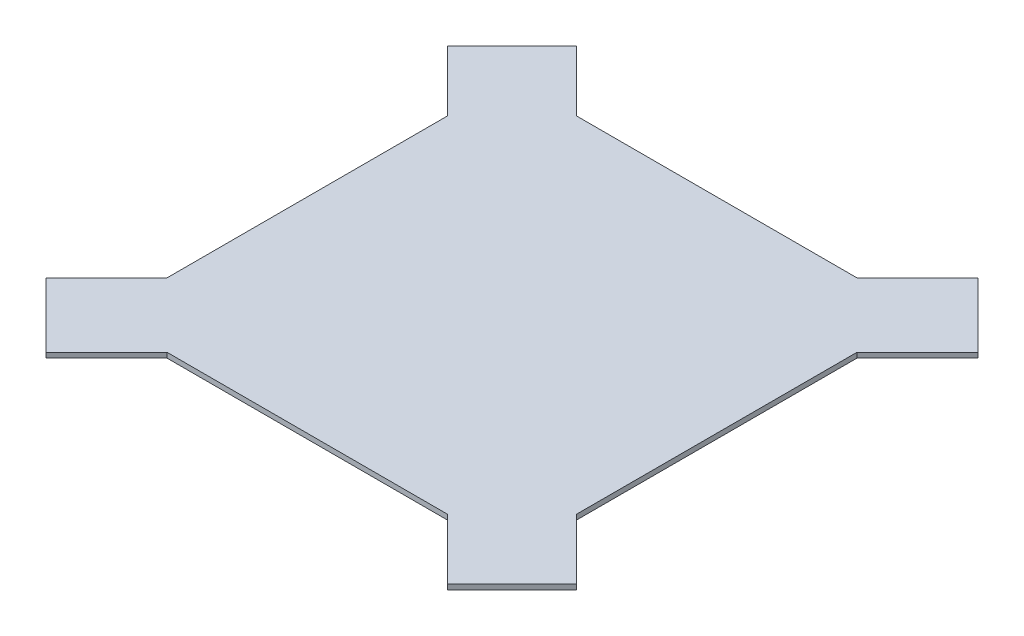
SolidWorks part; units mm, degrees
note: The reader was unsure of these and kept them because the rebuilt part matched: shared geometry of "Sketch39<3>".
ref_plane "Front Plane" through (0, 0, 0) normal (0, 0, 1) x (1, 0, 0)
ref_plane "Top Plane" through (0, 0, 0) normal (0, 1, 0) x (1, 0, 0)
ref_plane "Right Plane" through (0, 0, 0) normal (1, 0, 0) x (0, 0, -1)
sketch "Sketch1" plane through (0, 0, 0) normal (0, 1, 0) x (1, 0, 0)
  line L0 (0, 0) -> (-203.2, 0) construction
  line L1 (254, -381) -> (-254, -381)
  line L2 (381, -254) -> (381, 254)
  line L3 (254, 381) -> (-254, 381)
  line L4 (-381, -254) -> (-381, 254)
  line L5 (381, -381) -> (-381, 381) construction
  line L6 (381, 381) -> (-381, -381) construction
  line L7 (203.2, 152.4) -> (-203.2, 152.4)
  line L8 (203.2, 152.4) -> (203.2, -152.4)
  line L9 (203.2, -152.4) -> (-203.2, -152.4)
  line L10 (-203.2, 152.4) -> (-203.2, -152.4) construction
  line L11 (0, 0) -> (0, 152.4) construction
  line L12 (-254, -381) -> (-381, -254)
  line L13 (-254, 381) -> (-381, 254)
  line L14 (381, 254) -> (254, 381)
  line L15 (381, -254) -> (254, -381)
  point P0 (0, 0)
  point P6 (0, 0)
  dimension "D1" = 762
  dimension "D2" = 762
  dimension "D3" = 304.8
  dimension "D4" = 406.4
  dimension "D5" = 127
  dimension "D6" = 45
  dimension "D7" = 127
  dimension "D8" = 45
  dimension "D9" = 127
  dimension "D10" = 45
  dimension "D11" = 127
  dimension "D12" = 45
extrude "Boss-Extrude1" add sketch "Sketch1" against normal blind 6.35
sketch "Sketch2" [suppressed] plane through (0, 0, 0) normal (0, 1, 0) x (1, 0, 0)
  line L0 (640.2073, 0) -> (-640.2073, 0) construction
  line L1 (0, 0) -> (0, 687.3175) construction
  line L2 (-203.2, 152.4) -> (-203.2, -152.4) construction
  line L3 (203.2, 152.4) -> (-203.2, 152.4) construction
  line L4 (203.2, -152.4) -> (203.2, 152.4) construction
  line L5 (-203.2, -152.4) -> (203.2, -152.4) construction
  line L6 (203.2, 152.4) -> (-203.2, 152.4)
  line L7 (203.2, -152.4) -> (203.2, 152.4)
  line L8 (-203.2, -152.4) -> (203.2, -152.4)
  line L9 (-203.2, 152.4) -> (-203.2, -152.4)
  line L10 (-215.9, 165.1) -> (-215.9, -165.1)
  line L11 (-215.9, -165.1) -> (215.9, -165.1)
  line L12 (215.9, -165.1) -> (215.9, 165.1)
  line L13 (215.9, 165.1) -> (-215.9, 165.1)
  line L14 (203.2, -152.4) -> (228.6, -152.4) construction
  line L15 (228.6, 152.4) -> (203.2, 152.4) construction
  line L16 (228.6, -152.4) -> (215.9, -152.4)
  line L17 (228.6, 152.4) -> (215.9, 152.4)
  line L18 (222.25, -152.4) -> (222.25, 152.4) construction
  line L19 (222.25, 0) -> (374.65, 0) construction
  line L20 (381, -152.4) -> (368.3, -152.4)
  line L21 (381, -254) -> (381, 254) construction
  line L22 (368.3, -152.4) -> (368.3, 152.4)
  line L23 (368.3, 152.4) -> (381, 152.4)
  line L24 (374.65, -152.4) -> (374.65, 152.4) construction
  line L25 (374.65, 0) -> (222.25, 152.4) construction
  line L26 (222.25, 0) -> (374.65, 152.4) construction
  line L27 (374.65, 0) -> (222.25, -152.4) construction
  line L28 (222.25, 0) -> (374.65, -152.4) construction
  line L29 (217.7599, 0) -> (372.4049, 154.6451)
  line L30 (217.7599, 0) -> (372.4049, -154.6451)
  line L31 (370.1599, 0) -> (220.0049, 150.1549)
  line L32 (370.1599, 0) -> (220.0049, -150.1549)
  line L33 (-114.3, -246.761) -> (0, -246.761) construction
  line L34 (-114.3, -350.139) -> (0, -350.139) construction
  line L35 (-114.3, -243.586) -> (0, -243.586)
  line L36 (-114.3, -353.314) -> (0, -353.314)
  line L37 (-114.3, -249.936) -> (0, -249.936)
  line L38 (-114.3, -346.964) -> (0, -346.964)
  line L39 (-114.3, 350.139) -> (-176.911, 350.139) construction
  line L40 (-374.65, 152.4) -> (-176.911, 350.139) construction
  line L41 (-114.3, 246.761) -> (-197.739, 246.761) construction
  line L42 (-197.739, 246.761) -> (-368.3, 76.2) construction
  line L43 (-222.25, 152.4) -> (-352.425, 282.575) construction
  line L44 (-222.25, -152.4) -> (-352.425, -282.575) construction
  line L45 (-368.3, -76.2) -> (-298.45, -76.2) construction
  line L46 (-197.739, -246.761) -> (-368.3, -76.2) construction
  line L47 (-114.3, -246.761) -> (-197.739, -246.761) construction
  line L48 (-374.65, -152.4) -> (-176.911, -350.139) construction
  line L49 (-114.3, -350.139) -> (-176.911, -350.139) construction
  line L50 (-222.25, 0) -> (-374.65, -152.4) construction
  line L51 (228.6, -152.4) -> (228.6, 152.4)
  line L52 (226.7401, 0) -> (376.8951, 150.1549)
  line L53 (226.7401, 0) -> (376.8951, -150.1549)
  line L54 (379.1401, 0) -> (224.4951, 154.6451)
  line L55 (379.1401, 0) -> (224.4951, -154.6451)
  line L56 (114.3, -353.314) -> (114.3, -346.964) construction
  line L57 (114.3, -350.139) -> (176.911, -350.139) construction
  line L58 (374.65, -152.4) -> (176.911, -350.139) construction
  line L59 (114.3, -350.139) -> (0, -350.139) construction
  line L60 (114.3, -249.936) -> (114.3, -243.586) construction
  line L61 (114.3, -246.761) -> (0, -246.761) construction
  line L62 (114.3, -246.761) -> (197.739, -246.761) construction
  line L63 (197.739, -246.761) -> (368.3, -76.2) construction
  line L64 (368.3, -76.2) -> (298.45, -76.2) construction
  line L65 (222.25, -152.4) -> (352.425, -282.575) construction
  line L66 (254, -381) -> (381, -254) construction
  line L67 (217.7599, -152.4) -> (350.1799, -284.8201)
  line L68 (224.4951, -150.1549) -> (354.6701, -280.3299)
  line L69 (220.0049, -154.6451) -> (350.1799, -284.8201) construction
  line L70 (114.3, 246.761) -> (-114.3, 246.761) construction
  line L71 (114.3, 350.139) -> (-114.3, 350.139) construction
  line L72 (114.3, 243.586) -> (-114.3, 243.586)
  line L73 (372.4049, -150.1549) -> (175.5959, -346.964)
  line L74 (114.3, -346.964) -> (175.5959, -346.964)
  line L75 (114.3, -346.964) -> (0, -346.964)
  line L76 (114.3, -249.936) -> (0, -249.936)
  line L77 (114.3, -249.936) -> (199.0541, -249.936)
  line L78 (199.0541, -249.936) -> (368.3, -80.6901)
  line L79 (379.1401, -152.4) -> (178.2261, -353.314)
  line L80 (114.3, -353.314) -> (178.2261, -353.314)
  line L81 (114.3, -353.314) -> (0, -353.314)
  line L82 (114.3, -243.586) -> (0, -243.586)
  line L83 (114.3, -243.586) -> (196.4239, -243.586)
  line L84 (196.4239, -243.586) -> (368.3, -71.7099)
  line L85 (196.4239, -243.586) -> (366.0549, -73.9549) construction
  line L86 (376.8951, -154.6451) -> (178.2261, -353.314) construction
  line L87 (114.3, 353.314) -> (-114.3, 353.314)
  line L88 (199.0541, -249.936) -> (370.5451, -78.4451) construction
  line L89 (114.3, 249.936) -> (-114.3, 249.936)
  line L90 (114.3, 346.964) -> (-114.3, 346.964)
  line L91 (222.25, 152.4) -> (352.425, 282.575) construction
  line L92 (197.739, 246.761) -> (368.3, 76.2) construction
  line L93 (114.3, 246.761) -> (197.739, 246.761) construction
  line L94 (374.65, 152.4) -> (176.911, 350.139) construction
  line L95 (114.3, 350.139) -> (176.911, 350.139) construction
  line L96 (196.4239, 243.586) -> (368.3, 71.7099)
  line L97 (114.3, 243.586) -> (196.4239, 243.586)
  line L98 (114.3, 353.314) -> (178.2261, 353.314)
  line L99 (379.1401, 152.4) -> (178.2261, 353.314)
  line L100 (199.0541, 249.936) -> (368.3, 80.6901)
  line L101 (114.3, 249.936) -> (199.0541, 249.936)
  line L102 (114.3, 346.964) -> (175.5959, 346.964)
  line L103 (372.4049, 150.1549) -> (175.5959, 346.964)
  line L104 (224.4951, 150.1549) -> (354.6701, 280.3299)
  line L105 (217.7599, 152.4) -> (350.1799, 284.8201)
  line L106 (-374.65, 0) -> (-222.25, -152.4) construction
  line L107 (-222.25, 0) -> (-374.65, 152.4) construction
  line L108 (-374.65, 0) -> (-222.25, 152.4) construction
  line L109 (-374.65, -152.4) -> (-374.65, 152.4) construction
  line L110 (-222.25, 0) -> (-374.65, 0) construction
  line L111 (-222.25, -152.4) -> (-222.25, 152.4) construction
  line L112 (-217.7599, 152.4) -> (-350.1799, 284.8201)
  line L113 (-224.4951, 150.1549) -> (-354.6701, 280.3299)
  line L114 (-372.4049, 150.1549) -> (-175.5959, 346.964)
  line L115 (-114.3, 346.964) -> (-175.5959, 346.964)
  line L116 (-114.3, 249.936) -> (-199.0541, 249.936)
  line L117 (-199.0541, 249.936) -> (-368.3, 80.6901)
  line L118 (-379.1401, 152.4) -> (-178.2261, 353.314)
  line L119 (-114.3, 353.314) -> (-178.2261, 353.314)
  line L120 (-114.3, 243.586) -> (-196.4239, 243.586)
  line L121 (-196.4239, 243.586) -> (-368.3, 71.7099)
  line L122 (-196.4239, -243.586) -> (-368.3, -71.7099)
  line L123 (-114.3, -243.586) -> (-196.4239, -243.586)
  line L124 (-114.3, -353.314) -> (-178.2261, -353.314)
  line L125 (-379.1401, -152.4) -> (-178.2261, -353.314)
  line L126 (-199.0541, -249.936) -> (-368.3, -80.6901)
  line L127 (-114.3, -249.936) -> (-199.0541, -249.936)
  line L128 (-114.3, -346.964) -> (-175.5959, -346.964)
  line L129 (-372.4049, -150.1549) -> (-175.5959, -346.964)
  line L130 (-224.4951, -150.1549) -> (-354.6701, -280.3299)
  line L131 (-217.7599, -152.4) -> (-350.1799, -284.8201)
  line L132 (-379.1401, 0) -> (-224.4951, -154.6451)
  line L133 (-379.1401, 0) -> (-224.4951, 154.6451)
  line L134 (-226.7401, 0) -> (-376.8951, -150.1549)
  line L135 (-226.7401, 0) -> (-376.8951, 150.1549)
  line L136 (-228.6, -152.4) -> (-228.6, 152.4)
  line L137 (-370.1599, 0) -> (-220.0049, -150.1549)
  line L138 (-370.1599, 0) -> (-220.0049, 150.1549)
  line L139 (-217.7599, 0) -> (-372.4049, -154.6451)
  line L140 (-217.7599, 0) -> (-372.4049, 154.6451)
  line L141 (-368.3, 152.4) -> (-381, 152.4)
  line L142 (-368.3, -152.4) -> (-368.3, 152.4)
  line L143 (-381, -152.4) -> (-368.3, -152.4)
  line L144 (-228.6, 152.4) -> (-215.9, 152.4)
  line L145 (-228.6, -152.4) -> (-215.9, -152.4)
  line L146 (-368.3, -248.7395) -> (-248.7395, -368.3)
  line L147 (-248.7395, -368.3) -> (248.7395, -368.3)
  line L148 (248.7395, -368.3) -> (368.3, -248.7395)
  line L149 (368.3, -248.7395) -> (368.3, 248.7395)
  line L150 (368.3, 248.7395) -> (248.7395, 368.3)
  line L151 (248.7395, 368.3) -> (-248.7395, 368.3)
  line L152 (-248.7395, 368.3) -> (-368.3, 248.7395)
  line L153 (-368.3, 248.7395) -> (-368.3, -248.7395)
  line L154 (-381, -254) -> (-254, -381)
  line L155 (-254, -381) -> (254, -381)
  line L156 (254, -381) -> (381, -254)
  line L157 (381, -254) -> (381, 254)
  line L158 (381, 254) -> (254, 381)
  line L159 (254, 381) -> (-254, 381)
  line L160 (-254, 381) -> (-381, 254)
  line L161 (-381, 254) -> (-381, -254)
  line L162 (-381, -254) -> (-254, -381)
  line L163 (-254, -381) -> (254, -381)
  line L164 (254, -381) -> (381, -254)
  line L165 (381, -254) -> (381, 254)
  line L166 (381, 254) -> (254, 381)
  line L167 (254, 381) -> (-254, 381)
  line L168 (-254, 381) -> (-381, 254)
  line L169 (-381, 254) -> (-381, -254)
  line L170 (-304.8, 0) -> (-222.25, -82.55)
  line L171 (-304.8, 0) -> (-222.25, 82.55)
  line L172 (-300.3099, 0) -> (-220.0049, -80.3049)
  line L173 (-300.3099, 0) -> (-220.0049, 80.3049)
  line L174 (-309.2901, 0) -> (-224.4951, -84.7951)
  line L175 (-309.2901, 0) -> (-224.4951, 84.7951)
  line L176 (-222.25, 0) -> (-374.65, 0) construction
  line L177 (-222.25, 3.175) -> (-374.65, 3.175)
  line L178 (-222.25, -3.175) -> (-374.65, -3.175)
  line L179 (222.25, 0) -> (374.65, 0) construction
  line L180 (222.25, 0) -> (374.65, 0) construction
  line L181 (222.25, -3.175) -> (374.65, -3.175)
  line L182 (222.25, 3.175) -> (374.65, 3.175)
  line L183 (309.2901, 0) -> (224.4951, 84.7951)
  line L184 (309.2901, 0) -> (224.4951, -84.7951)
  line L185 (300.3099, 0) -> (220.0049, 80.3049)
  line L186 (300.3099, 0) -> (220.0049, -80.3049)
  line L187 (304.8, 0) -> (222.25, 82.55)
  line L188 (304.8, 0) -> (222.25, -82.55)
  circle A0 centre (-114.3, -298.45) radius 48.514
  circle A2 centre (114.3, -298.45) radius 48.514
  circle A3 centre (-114.3, 298.45) radius 48.514
  circle A4 centre (114.3, 298.45) radius 48.514
  circle A5 centre (-114.3, -298.45) radius 54.864
  circle A6 centre (114.3, 298.45) radius 54.864
  circle A7 centre (114.3, -298.45) radius 54.864
  circle A8 centre (-114.3, 298.45) radius 54.864
  point P65 (0, 350.139)
  point P68 (0, 246.761)
  point P70 (0, 346.964)
  point P72 (0, 249.936)
  point P74 (0, 353.314)
  point P76 (0, 243.586)
  dimension "D3" = 97.028
  dimension "D1" = 114.3
  dimension "D2" = 298.45
  dimension "D9" = 3.175
  dimension "D10" = 3.175
  dimension "D11" = 3.175
  dimension "D14" = 3.175
  dimension "D15" = 3.175
  dimension "D16" = 0
  dimension "D7" = 12.7
  dimension "D8" = 12.7
  dimension "D12" = 45
  dimension "D18" = 76.2
  dimension "D4" = 6.35
  dimension "D5" = 6.35
  dimension "D6" = 12.7
  dimension "D13" = 3.175
  dimension "D17" = 12.7
  dimension "D19" = 3.175
  dimension "D20" = 3.175
  dimension "D21" = 3.175
  dimension "D22" = 3.175
sketch "Sketch3" plane through (0, 0, 0) normal (0, 1, 0) x (1, 0, 0)
  line L0 (-251.0461, -331.8684) -> (-175.26, -256.0823)
  line L1 (-254, -381) -> (-381, -254) construction
  line L2 (-175.26, -256.0823) -> (-175.26, -381)
  line L3 (254, -381) -> (-254, -381) construction
  line L4 (-120.65, -224.79) -> (-120.65, -526.5709) construction
  line L5 (-120.65, -279.4) -> (-175.26, -279.4) construction
  line L6 (-317.5, -317.5) -> (0, 0) construction
  line L7 (-331.8684, -251.0461) -> (-256.0823, -175.26)
  line L8 (-256.0823, -175.26) -> (-256.0823, 0)
  line L9 (-3.4925, 0) -> (3.4925, 0) construction
  line L10 (-66.04, -256.0823) -> (-66.04, -381)
  line L11 (-66.04, -256.0823) -> (0, -256.0823)
  line L12 (0, 0) -> (-591.5998, 0) construction
  line L13 (0, 0) -> (0, 686.1368) construction
  line L14 (0, -256.0823) -> (0, -381)
  line L15 (-256.0823, 0) -> (-381, 0)
  line L16 (-381, -254) -> (-381, 254) construction
  line L18 (-66.04, 256.0823) -> (-66.04, 381)
  line L37 (-246.6957, -307.482) -> (-307.482, -246.6957) construction
  line L38 (-251.0461, -331.8684) -> (-331.8684, -251.0461)
  circle A0 centre (-120.65, -279.4) radius 54.61
  circle A1 centre (-120.65, -279.4) radius 48.26
  circle A8 centre (-246.6957, -307.482) radius 3.175 construction
  circle A9 centre (-307.482, -246.6957) radius 3.175 construction
  point P0 (-251.0461, -331.8684)
  point P9 (-333.6238, -249.2907)
  point P23 (-277.0888, -277.0888)
  point P29 (-120.5346, -271.04)
  point P31 (-65.9246, -271.04)
  point P32 (-331.8684, -251.0461)
  point P44 (-256.0823, 0)
  point P71 (0, 256.0823)
  point P72 (0, -256.0823)
  dimension "D2" = 101.6
  dimension "D4" = 6.35
  dimension "D1" = 109.22
  dimension "D7" = 6.35
  dimension "D3" = 85.9648
  dimension "D5" = 114.3
  dimension "D6" = 57.15
  dimension "D8" = 20.32
  dimension "D10" = 120.65
extrude "Cut-Extrude1" cut sketch "Sketch3" against normal up to next
hole_wizard "#4 Clearance Hole2" [suppressed] positions "Sketch17" profile "Sketch19" hole size "#4" standard "ANSI Inch"
sketch "Sketch17" plane through (0, 0, 0) normal (0, 1, 0) x (1, 0, 0)
  point P0 (-307.482, -246.6957)
  point P3 (-246.6957, -307.482)
sketch "Sketch19" plane through (-307.482, 0, 246.6957) normal (1, 0, 0) x (0, 0, 1)
  line L0 (0, 0) -> (0, 6.35)
  line L1 (0, 6.35) -> (1.4732, 6.35)
  line L2 (1.4732, 6.35) -> (1.4732, 0)
  line L5 (1.4732, 0) -> (0, 0)
  line L11 (0, -6.35) -> (0, 107.95) construction
  dimension "Thru Hole Dia." = 2.9464
  dimension "Thru Hole Depth" = 6.35
mirror "Mirror1" about plane through (0, 0, 0) normal (1, 0, 0) of "#4 Clearance Hole2", "Cut-Extrude1"
mirror "Mirror2" about plane through (0, 0, 0) normal (0, 0, 1) of "Mirror1", "Cut-Extrude1"
sketch "Sketch12" [suppressed] plane through (0, 0, 0) normal (0, 1, 0) x (1, 0, 0)
  line L0 (120.65, -279.4) -> (120.65, -223.52) construction
  line L1 (120.65, -223.52) -> (132.08, -223.52) construction
  line L2 (120.65, -279.4) -> (132.08, -223.52) construction
  circle A0 centre (120.65, -279.4) radius 48.26 construction
  circle A1 centre (120.65, -279.4) radius 48.26 construction
  circle A2 centre (132.08, -223.52) radius 2.9268
  circle A3 centre (126.365, -233.4187) radius 2.9268 [skipped]
  circle A4 centre (114.935, -233.4187) radius 2.9268 [skipped]
  circle A5 centre (109.22, -223.52) radius 2.9268
  circle A8 centre (114.935, -213.6214) radius 2.9268 [skipped]
  circle A9 centre (126.365, -213.6214) radius 2.9268 [skipped]
  point P8 (120.65, -223.52)
  point P19 (120.65, -223.52)
  dimension "D3" = 5.8535
  dimension "D1" = 57.037
  dimension "D2" = 22.86
  dimension "D4" = 6
hole_wizard "#4 Clearance Hole1" [suppressed] positions "Sketch14" profile "Sketch16" hole size "#4" standard "ANSI Inch"
sketch "Sketch14" [suppressed] plane through (0, 0, 0) normal (0, 1, 0) x (1, 0, 0)
  point P0 (109.22, -223.52)
  point P3 (132.08, -223.52)
sketch "Sketch16" [suppressed] plane through (109.22, 0, 223.52) normal (1, 0, 0) x (0, 0, 1)
  line L0 (0, 0) -> (0, 6.35)
  line L1 (0, 6.35) -> (1.6319, 6.35)
  line L2 (1.6319, 6.35) -> (1.6319, 0)
  line L5 (1.6319, 0) -> (0, 0)
  line L11 (0, -6.35) -> (0, 107.95) construction
  dimension "Thru Hole Dia." = 3.2639
  dimension "Thru Hole Depth" = 6.35
sketch "Sketch13" [suppressed] plane through (0, -6.35, 0) normal (0, -1, 0) x (1, 0, 0)
  line L0 (-307.482, -246.6957) -> (-287.3581, -266.8195) construction
  line L1 (-287.3581, -266.8195) -> (-266.8195, -287.3581) construction
  line L2 (-266.8195, -287.3581) -> (-246.6957, -307.482) construction
  line L3 (-278.3779, -257.8393) -> (-257.8393, -278.3779)
  line L4 (-296.3384, -275.7998) -> (-275.7998, -296.3384)
  arc A0 (-278.3779, -257.8393) -> (-296.3384, -275.7998) centre (-287.3581, -266.8195) ccw
  arc A2 (-275.7998, -296.3384) -> (-257.8393, -278.3779) centre (-266.8195, -287.3581) ccw
  dimension "D1" = 29.046
  dimension "D2" = 25.4
extrude "Cut-Extrude10" [suppressed] cut sketch "Sketch13" against normal through all
mirror "Mirror3" [suppressed] about plane through (0, 0, 0) normal (1, 0, 0)
mirror "Mirror4" [suppressed] about plane through (0, 0, 0) normal (0, 0, 1)
sketch "Sketch4" [suppressed] plane through (0, 0, 0) normal (0, 1, 0) x (1, 0, 0)
  line L22 (-182.88, 152.4) -> (-182.88, 170.18) construction
  line L23 (-203.2, -152.4) -> (203.2, -152.4) construction
  line L24 (-203.2, -152.4) -> (-203.2, 152.4) construction
  line L25 (-203.2, 152.4) -> (203.2, 152.4) construction
  line L26 (203.2, -152.4) -> (203.2, 152.4) construction
  line L27 (-203.2, -152.4) -> (203.2, 152.4) construction
  line L28 (-203.2, 152.4) -> (203.2, -152.4) construction
  line L29 (-182.88, 170.18) -> (-220.98, 170.18) construction
  line L30 (-220.98, 170.18) -> (-220.98, 132.08) construction
  line L31 (-220.98, 132.08) -> (-203.2, 132.08) construction
  line L32 (-203.2, 152.4) -> (-220.98, 170.18) construction
  line L33 (-214.63, 132.08) -> (-214.63, 138.43) construction
  line L39 (-214.63, 138.43) -> (-214.63, 151.13) construction
  line L40 (-214.63, 151.13) -> (-214.63, 163.83) construction
  line L41 (203.2, 0) -> (-203.2, 0) construction
  line L42 (0, 152.4) -> (0, -152.4) construction
  line L43 (0, 163.83) -> (12.7, 163.83) construction
  line L44 (12.7, 163.83) -> (25.4, 163.83) construction
  line L45 (25.4, 163.83) -> (31.75, 163.83) construction
  line L46 (25.4, -163.83) -> (31.75, -163.83) construction
  line L47 (12.7, -163.83) -> (25.4, -163.83) construction
  line L48 (0, -163.83) -> (12.7, -163.83) construction
  circle A29 centre (-214.63, 138.43) radius 2.5527
  circle A30 centre (-214.63, 151.13) radius 2.5527
  circle A31 centre (-214.63, 163.83) radius 2.5527
  circle A32 centre (-201.93, 163.83) radius 2.5527
  circle A33 centre (-189.23, 163.83) radius 2.5527
  circle A34 centre (0, 163.83) radius 2.5527
  circle A35 centre (25.4, 163.83) radius 2.5527
  circle A36 centre (12.7, 163.83) radius 2.5527
  circle A37 centre (-12.7, 163.83) radius 2.5527
  circle A38 centre (-25.4, 163.83) radius 2.5527
  circle A39 centre (201.93, 163.83) radius 2.5527
  circle A40 centre (189.23, 163.83) radius 2.5527
  circle A41 centre (214.63, 163.83) radius 2.5527
  circle A42 centre (214.63, 151.13) radius 2.5527
  circle A43 centre (214.63, 138.43) radius 2.5527
  circle A44 centre (-214.63, -138.43) radius 2.5527
  circle A45 centre (-214.63, -151.13) radius 2.5527
  circle A46 centre (-214.63, -163.83) radius 2.5527
  circle A47 centre (-189.23, -163.83) radius 2.5527
  circle A48 centre (-201.93, -163.83) radius 2.5527
  circle A49 centre (-25.4, -163.83) radius 2.5527
  circle A50 centre (-12.7, -163.83) radius 2.5527
  circle A51 centre (12.7, -163.83) radius 2.5527
  circle A52 centre (25.4, -163.83) radius 2.5527
  circle A53 centre (0, -163.83) radius 2.5527
  circle A54 centre (189.23, -163.83) radius 2.5527
  circle A55 centre (201.93, -163.83) radius 2.5527
  circle A56 centre (214.63, -138.43) radius 2.5527
  circle A57 centre (214.63, -151.13) radius 2.5527
  circle A58 centre (214.63, -163.83) radius 2.5527
  point P0 (0, 0)
  point P12 (-214.63, 138.43)
  point P14 (-214.63, 151.13)
  dimension "D6" = 6.35
  dimension "D7" = 5.1054
  dimension "D8" = 5.1054
  dimension "D1" = 304.8
  dimension "D2" = 406.4
  dimension "D3" = 38.1
  dimension "D4" = 17.78
  dimension "D5" = 6.35
  dimension "D9" = 11.43
  dimension "D10" = 31.75
  dimension "D11" = 6.35
hole_wizard "#4-40 Tapped Hole1" [suppressed] positions "Sketch20" profile "Sketch21" tap size "#4-40" standard "ANSI Inch"
sketch "Sketch20" [suppressed] plane through (0, -6.35, 0) normal (0, -1, 0) x (-1, 0, 0)
  line L0 (214.63, 138.43) -> (214.63, 151.13) construction
  point P0 (189.23, -163.83)
  point P3 (201.93, -163.83)
  point P6 (214.63, -163.83)
  point P9 (214.63, -151.13)
  point P12 (214.63, -138.43)
  point P15 (25.4, -163.83)
  point P18 (12.7, -163.83)
  point P21 (0, -163.83)
  point P24 (-12.7, -163.83)
  point P27 (-25.4, -163.83)
  point P30 (-189.23, -163.83)
  point P33 (-201.93, -163.83)
  point P36 (-214.63, -163.83)
  point P39 (-214.63, -151.13)
  point P42 (-214.63, -138.43)
  point P46 (214.63, 138.43)
  point P49 (214.63, 151.13)
  point P58 (214.63, 163.83)
  point P61 (201.93, 163.83)
  point P64 (189.23, 163.83)
  point P67 (25.4, 163.83)
  point P70 (12.7, 163.83)
  point P73 (0, 163.83)
  point P76 (-12.7, 163.83)
  point P79 (-25.4, 163.83)
  point P82 (-214.63, 163.83)
  point P85 (-214.63, 151.13)
  point P88 (-214.63, 138.43)
  point P91 (-201.93, 163.83)
  point P94 (-189.23, 163.83)
sketch "Sketch21" [suppressed] plane through (-189.23, -6.35, 163.83) normal (1, 0, 0) x (0, 0, -1)
  line L0 (0, 0) -> (0, 6.35)
  line L1 (0, 6.35) -> (1.1303, 6.35)
  line L2 (1.1303, 6.35) -> (1.1303, 0)
  line L5 (1.1303, 0) -> (0, 0)
  line L11 (0, -6.35) -> (0, 107.95) construction
  dimension "Thru Tap Drill Dia." = 2.2606
  dimension "Thru Tap Drill Depth" = 6.35
cosmetic thread "Hole Thread3" [suppressed] parameters "D2"=2.8448
cosmetic thread "Hole Thread4" [suppressed] parameters "D2"=2.8448
cosmetic thread "Hole Thread5" [suppressed] parameters "D2"=2.8448
cosmetic thread "Hole Thread6" [suppressed] parameters "D2"=2.8448
cosmetic thread "Hole Thread7" [suppressed] parameters "D2"=2.8448
cosmetic thread "Hole Thread8" [suppressed] parameters "D2"=2.8448
cosmetic thread "Hole Thread9" [suppressed] parameters "D2"=2.8448
cosmetic thread "Hole Thread10" [suppressed] parameters "D2"=2.8448
cosmetic thread "Hole Thread11" [suppressed] parameters "D2"=2.8448
cosmetic thread "Hole Thread12" [suppressed] parameters "D2"=2.8448
cosmetic thread "Hole Thread13" [suppressed] parameters "D2"=2.8448
cosmetic thread "Hole Thread14" [suppressed] parameters "D2"=2.8448
cosmetic thread "Hole Thread15" [suppressed] parameters "D2"=2.8448
cosmetic thread "Hole Thread16" [suppressed] parameters "D2"=2.8448
cosmetic thread "Hole Thread17" [suppressed] parameters "D2"=2.8448
cosmetic thread "Hole Thread18" [suppressed] parameters "D2"=2.8448
cosmetic thread "Hole Thread19" [suppressed] parameters "D2"=2.8448
cosmetic thread "Hole Thread20" [suppressed] parameters "D2"=2.8448
cosmetic thread "Hole Thread21" [suppressed] parameters "D2"=2.8448
cosmetic thread "Hole Thread22" [suppressed] parameters "D2"=2.8448
cosmetic thread "Hole Thread23" [suppressed] parameters "D2"=2.8448
cosmetic thread "Hole Thread24" [suppressed] parameters "D2"=2.8448
cosmetic thread "Hole Thread25" [suppressed] parameters "D2"=2.8448
cosmetic thread "Hole Thread26" [suppressed] parameters "D2"=2.8448
cosmetic thread "Hole Thread27" [suppressed] parameters "D2"=2.8448
cosmetic thread "Hole Thread28" [suppressed] parameters "D2"=2.8448
cosmetic thread "Hole Thread29" [suppressed] parameters "D2"=2.8448
cosmetic thread "Hole Thread30" [suppressed] parameters "D2"=2.8448
cosmetic thread "Hole Thread31" [suppressed] parameters "D2"=2.8448
cosmetic thread "Hole Thread32" [suppressed] parameters "D2"=2.8448
sketch "Sketch5" [suppressed] plane through (0, 0, 0) normal (0, 1, 0) x (1, 0, 0)
  line L6 (-88.9, -44.45) -> (88.9, -44.45)
  line L12 (-88.9, -44.45) -> (-88.9, 44.45)
  line L13 (-88.9, 44.45) -> (88.9, 44.45)
  line L14 (88.9, -44.45) -> (88.9, 44.45)
  line L15 (-88.9, -44.45) -> (88.9, 44.45) construction
  line L16 (-88.9, 44.45) -> (88.9, -44.45) construction
  point P0 (0, 0)
  dimension "D1" = 88.9
  dimension "D2" = 177.8
extrude "Cut-Extrude3" [suppressed] cut sketch "Sketch5" against normal up to next
fillet "Fillet1" [suppressed] radius 8.89
sketch "Sketch8" [suppressed] plane through (0, 0, 0) normal (0, 1, 0) x (1, 0, 0)
  line L0 (66.04, 256.0823) -> (-66.04, 256.0823) construction
  line L1 (66.04, 256.0823) -> (66.04, 279.4) construction
  line L2 (0, 0) -> (0, -256.0823) construction
  line L3 (0, 0) -> (256.0823, 0) construction
  line L4 (256.0823, -175.26) -> (256.0823, 175.26) construction
  line L5 (-66.04, -256.0823) -> (66.04, -256.0823) construction
  circle A0 centre (78.74, 201.4723) radius 10
  circle A1 centre (-78.74, 201.4723) radius 10
  circle A2 centre (-78.74, -201.4723) radius 10
  circle A3 centre (78.74, -201.4723) radius 10
  dimension "D1" = 20
  dimension "D2" = 54.61
  dimension "D3" = 12.7
extrude "Cut-Extrude6" [suppressed] cut sketch "Sketch8" against normal up to next
hole_wizard "#10-32 Tapped Hole2" [suppressed] positions "Sketch24" profile "Sketch25" tap size "#10-32" standard "ANSI Inch"
sketch "Sketch24" plane through (0, -6.35, 0) normal (0, -1, 0) x (-1, 0, 0)
  line L3 (0, 0) -> (256.0823, 0) construction
  line L4 (256.0823, 175.26) -> (256.0823, -175.26) construction
  line L6 (228.6, 0) -> (228.6, 25.4) construction
  line L7 (228.6, 25.4) -> (256.0823, 25.4) construction
  point P143 (228.6, 25.4)
  dimension "D1" = 228.6
  dimension "D2" = 25.4
cosmetic thread "Hole Thread33" [suppressed] parameters "D2"=4.826
sketch "Sketch25" plane through (-228.6, -6.35, -25.4) normal (1, 0, 0) x (0, 0, -1)
  line L0 (0, 0) -> (0, 6.35)
  line L1 (0, 6.35) -> (2.0193, 6.35)
  line L2 (2.0193, 6.35) -> (2.0193, 0)
  line L5 (2.0193, 0) -> (0, 0)
  line L11 (0, -6.35) -> (0, 107.95) construction
  dimension "Thru Tap Drill Dia." = 4.0386
  dimension "Thru Tap Drill Depth" = 6.35
pattern_linear "LPattern1" [suppressed] count 6 spacing 25.4 count 3 spacing 50.8
hole_wizard "#10-32 Tapped Hole3" [suppressed] positions "Sketch26" profile "Sketch27" tap size "#10-32" standard "ANSI Inch"
sketch "Sketch26" plane through (0, -6.35, 0) normal (0, -1, 0) x (-1, 0, 0)
  line L0 (0, 0) -> (76.2, 0) construction
  line L1 (76.2, 0) -> (76.2, 76.2) construction
  point P0 (76.2, 76.2)
  dimension "D1" = 76.2
  dimension "D2" = 76.2
sketch "Sketch27" plane through (-76.2, -6.35, -76.2) normal (1, 0, 0) x (0, 0, -1)
  line L0 (0, 0) -> (0, 6.35)
  line L1 (0, 6.35) -> (2.0193, 6.35)
  line L2 (2.0193, 6.35) -> (2.0193, 0)
  line L5 (2.0193, 0) -> (0, 0)
  line L11 (0, -6.35) -> (0, 107.95) construction
  dimension "Thru Tap Drill Dia." = 4.0386
  dimension "Thru Tap Drill Depth" = 6.35
cosmetic thread "Hole Thread34" [suppressed] parameters "D2"=4.826
pattern_linear "LPattern2" [suppressed] count 4 spacing 25.4 count 2 spacing 50.8
mirror "Mirror7" [suppressed] about plane through (0, 0, 0) normal (1, 0, 0)
mirror "Mirror8" [suppressed] about plane through (0, 0, 0) normal (0, 0, 1)
fillet "Fillet5" [suppressed] radius 3.175
fillet "Fillet6" [suppressed] radius 12.7
sketch "Sketch22" [suppressed] plane through (0, -6.35, 0) normal (0, -1, 0) x (1, 0, 0)
  line L0 (0, 256.0823) -> (0, 210.3623) construction
  line L1 (-57.15, 182.4223) -> (57.15, 182.4223)
  line L3 (-57.15, 238.3023) -> (57.15, 238.3023)
  line L5 (-57.15, 182.4223) -> (57.15, 238.3023) construction
  line L6 (-57.15, 238.3023) -> (57.15, 182.4223) construction
  line L7 (53.34, 256.0823) -> (-53.34, 256.0823) construction
  line L8 (0, 210.3623) -> (0, 44.45) construction
  line L9 (80.01, 44.45) -> (-80.01, 44.45) construction
  line L10 (57.15, 238.3023) -> (95.25, 210.3623)
  line L11 (95.25, 210.3623) -> (57.15, 182.4223)
  line L12 (-57.15, 238.3023) -> (-95.25, 210.3623)
  line L13 (-95.25, 210.3623) -> (-57.15, 182.4223)
  line L14 (268.1086, 268.1086) -> (196.2665, 196.2665) construction
  line L15 (257.8393, 278.3779) -> (278.3779, 257.8393) construction
  line L16 (196.2665, 253.7402) -> (232.1876, 289.6612)
  line L17 (196.2665, 253.7402) -> (253.7402, 196.2665) construction
  line L18 (232.1876, 289.6612) -> (289.6612, 232.1876)
  line L19 (253.7402, 196.2665) -> (289.6612, 232.1876)
  line L20 (196.2665, 253.7402) -> (289.6612, 232.1876) construction
  line L21 (232.1876, 289.6612) -> (253.7402, 196.2665) construction
  line L22 (196.2665, 253.7402) -> (196.2665, 196.2665) construction
  line L23 (196.2665, 196.2665) -> (253.7402, 196.2665)
  line L24 (196.2665, 253.7402) -> (138.7929, 196.2665)
  line L25 (138.7929, 196.2665) -> (196.2665, 196.2665)
  point P0 (0, 210.3623)
  point P15 (242.9639, 242.9639)
  dimension "D1" = 114.3
  dimension "D2" = 55.88
  dimension "D3" = 17.78
  dimension "D4" = 38.1
  dimension "D5" = 81.28
  dimension "D6" = 50.8
  dimension "D7" = 10.16
extrude "Cut-Extrude11" [suppressed] cut sketch "Sketch22" against normal through all
sketch "Sketch23" [suppressed] plane through (0, -6.35, 0) normal (0, -1, 0) x (1, 0, 0)
  line L0 (57.15, 238.3023) -> (57.15, 182.4223) construction
  line L1 (57.15, 182.4223) -> (-57.15, 238.3023) construction
  line L2 (-57.15, 238.3023) -> (-57.15, 182.4223) construction
  line L3 (-57.15, 182.4223) -> (57.15, 238.3023) construction
  line L4 (-54.61, 186.4914) -> (-5.7831, 210.3623)
  line L5 (54.61, 186.4914) -> (5.7831, 210.3623)
  line L6 (-59.69, 242.3714) -> (-59.69, 178.3532)
  line L7 (59.69, 242.3714) -> (59.69, 178.3532)
  line L8 (59.69, 178.3532) -> (0, 207.535)
  line L9 (-54.61, 234.2332) -> (-54.61, 186.4914)
  line L10 (-59.69, 178.3532) -> (0, 207.535)
  line L11 (232.1876, 289.6612) -> (253.7402, 196.2665) construction
  line L12 (59.69, 238.3023) -> (59.69, 178.3532) construction
  line L13 (253.7402, 196.2665) -> (196.2665, 253.7402) construction
  line L14 (-59.69, 242.3714) -> (-59.69, 182.4223) construction
  line L15 (-56.0344, 180.1404) -> (58.2656, 236.0204) construction
  line L16 (-5.7831, 210.3623) -> (-54.61, 234.2332)
  line L17 (59.69, 178.3532) -> (-54.61, 234.2332) construction
  line L18 (0, 213.1896) -> (59.69, 242.3714)
  line L19 (5.7831, 210.3623) -> (54.61, 234.2332)
  line L20 (0, 213.1896) -> (-59.69, 242.3714)
  line L21 (54.61, 186.4914) -> (-59.69, 242.3714) construction
  line L22 (54.61, 234.2332) -> (54.61, 186.4914)
  line L23 (54.61, 238.3023) -> (54.61, 186.4914) construction
  line L24 (196.2665, 253.7402) -> (289.6612, 232.1876) construction
  line L25 (-54.61, 234.2332) -> (-54.61, 182.4223) construction
  line L26 (196.2665, 196.2665) -> (225.0034, 225.0034) construction
  line L27 (196.2665, 192.6744) -> (225.0034, 221.4113)
  line L28 (229.7126, 289.0901) -> (239.5751, 246.3527)
  line L29 (249.2738, 204.3251) -> (204.3251, 249.2738)
  line L31 (234.6625, 290.2323) -> (245.0819, 245.0819)
  line L32 (258.2066, 188.208) -> (225.0034, 221.4113)
  line L33 (204.3251, 249.2738) -> (240.8459, 240.8459)
  line L34 (188.208, 258.2066) -> (239.5751, 246.3527)
  line L36 (258.2066, 188.208) -> (194.4705, 251.9441) construction
  line L37 (196.8377, 256.2151) -> (290.2323, 234.6625) construction
  line L38 (290.2323, 234.6625) -> (289.0901, 229.7126)
  line L39 (229.7126, 289.0901) -> (234.6625, 290.2323)
  line L40 (198.8065, 190.1344) -> (165.7337, 223.2073) construction
  line L41 (198.0626, 194.4705) -> (226.7994, 223.2073) construction
  line L42 (221.4113, 225.0034) -> (198.8065, 247.6081)
  line L43 (245.0819, 245.0819) -> (290.2323, 234.6625)
  line L44 (246.3527, 239.5751) -> (258.2066, 188.208)
  line L45 (234.6625, 290.2323) -> (258.2066, 188.208) construction
  line L46 (246.3527, 239.5751) -> (289.0901, 229.7126)
  line L47 (195.6954, 251.2652) -> (289.0901, 229.7126) construction
  line L48 (240.8459, 240.8459) -> (249.2738, 204.3251)
  line L49 (229.7126, 289.0901) -> (249.2738, 204.3251) construction
  line L50 (196.2665, 196.2665) -> (225.0034, 225.0034) construction
  line L51 (249.2738, 204.3251) -> (198.0626, 255.5362) construction
  line L52 (196.2665, 253.7402) -> (196.2665, 196.2665) construction
  line L53 (196.2665, 253.7402) -> (196.2665, 196.2665) construction
  line L54 (196.2665, 196.2665) -> (167.5297, 225.0034) construction
  line L55 (196.2665, 253.7402) -> (138.7929, 196.2665) construction
  line L56 (193.7265, 252.6881) -> (193.7265, 202.3986)
  line L57 (193.7265, 202.3986) -> (169.3258, 226.7994)
  line L58 (193.7265, 253.7402) -> (193.7265, 202.3986) construction
  line L59 (196.2665, 192.6744) -> (165.7337, 223.2073)
  line L60 (165.7337, 223.2073) -> (169.3258, 226.7994)
  line L61 (198.8065, 202.3986) -> (221.4113, 225.0034)
  line L63 (198.8065, 253.7402) -> (198.8065, 190.1344) construction
  line L64 (198.8065, 247.6081) -> (198.8065, 202.3986)
  line L65 (193.7265, 252.6881) -> (188.208, 258.2066)
  dimension "D4" = 2.54
  dimension "D5" = 2.54
  dimension "D6" = 2.54
  dimension "D13" = 2.54
  dimension "D14" = 5.08
  dimension "D1" = 2.54
  dimension "D2" = 2.54
  dimension "D3" = 2.54
  dimension "D7" = 2.54
  dimension "D8" = 2.54
  dimension "D9" = 2.54
  dimension "D10" = 2.54
  dimension "D11" = 2.54
  dimension "D12" = 2.54
extrude "Boss-Extrude2" [suppressed] add sketch "Sketch23" against normal up to surface (6.35 mm away)
fillet "Fillet7" [suppressed] radius 3.81
mirror "Mirror5" [suppressed] about plane through (0, 0, 0) normal (1, 0, 0)
mirror "Mirror6" [suppressed] about plane through (0, 0, 0) normal (0, 0, 1)
sketch "Sketch28" [suppressed] plane through (0, -6.35, 0) normal (0, -1, 0) x (1, 0, 0)
  line L1 (-190.5, 127) -> (190.5, 127) construction
  line L2 (-190.5, 127) -> (-190.5, -127) construction
  line L3 (-190.5, -127) -> (190.5, -127) construction
  line L4 (190.5, 127) -> (190.5, -127) construction
  line L5 (-190.5, 127) -> (190.5, -127) construction
  line L6 (-190.5, -127) -> (190.5, 127) construction
  circle A0 centre (190.5, 127) radius 2.5527
  circle A1 centre (139.7, 127) radius 2.5527
  circle A2 centre (88.9, 127) radius 2.5527
  circle A3 centre (38.1, 127) radius 2.5527
  circle A4 centre (-12.7, 127) radius 2.5527
  circle A5 centre (-63.5, 127) radius 2.5527
  circle A6 centre (-114.3, 127) radius 2.5527
  circle A7 centre (-165.1, 127) radius 2.5527
  circle A8 centre (-215.9, 127) radius 2.5527
  circle A9 centre (139.7, 76.2) radius 2.5527
  circle A10 centre (88.9, 76.2) radius 2.5527
  circle A11 centre (38.1, 76.2) radius 2.5527
  circle A12 centre (-12.7, 76.2) radius 2.5527
  circle A13 centre (-63.5, 76.2) radius 2.5527
  circle A14 centre (-114.3, 76.2) radius 2.5527
  circle A15 centre (-165.1, 76.2) radius 2.5527
  circle A16 centre (-215.9, 76.2) radius 2.5527
  circle A17 centre (139.7, 25.4) radius 2.5527
  circle A18 centre (88.9, 25.4) radius 2.5527
  circle A19 centre (38.1, 25.4) radius 2.5527
  circle A20 centre (-12.7, 25.4) radius 2.5527
  circle A21 centre (-63.5, 25.4) radius 2.5527
  circle A22 centre (-114.3, 25.4) radius 2.5527
  circle A23 centre (-165.1, 25.4) radius 2.5527
  circle A24 centre (-215.9, 25.4) radius 2.5527
  circle A25 centre (139.7, -25.4) radius 2.5527
  circle A26 centre (88.9, -25.4) radius 2.5527
  circle A27 centre (38.1, -25.4) radius 2.5527
  circle A28 centre (-12.7, -25.4) radius 2.5527
  circle A29 centre (-63.5, -25.4) radius 2.5527
  circle A30 centre (-114.3, -25.4) radius 2.5527
  circle A31 centre (-165.1, -25.4) radius 2.5527
  circle A32 centre (-215.9, -25.4) radius 2.5527
  circle A33 centre (139.7, -76.2) radius 2.5527
  circle A34 centre (88.9, -76.2) radius 2.5527
  circle A35 centre (38.1, -76.2) radius 2.5527
  circle A36 centre (-12.7, -76.2) radius 2.5527
  circle A37 centre (-63.5, -76.2) radius 2.5527
  circle A38 centre (-114.3, -76.2) radius 2.5527
  circle A39 centre (-165.1, -76.2) radius 2.5527
  circle A40 centre (-215.9, -76.2) radius 2.5527
  circle A41 centre (139.7, -127) radius 2.5527
  circle A42 centre (88.9, -127) radius 2.5527
  circle A43 centre (38.1, -127) radius 2.5527
  circle A44 centre (-12.7, -127) radius 2.5527
  circle A45 centre (-63.5, -127) radius 2.5527
  circle A46 centre (-114.3, -127) radius 2.5527
  circle A47 centre (-165.1, -127) radius 2.5527
  circle A48 centre (-215.9, -127) radius 2.5527
  circle A49 centre (139.7, -177.8) radius 2.5527
  circle A50 centre (88.9, -177.8) radius 2.5527
  circle A51 centre (38.1, -177.8) radius 2.5527
  circle A52 centre (-12.7, -177.8) radius 2.5527
  circle A53 centre (-63.5, -177.8) radius 2.5527
  circle A54 centre (-114.3, -177.8) radius 2.5527
  circle A55 centre (-165.1, -177.8) radius 2.5527
  circle A56 centre (-215.9, -177.8) radius 2.5527
  circle A57 centre (190.5, 76.2) radius 2.5527
  circle A58 centre (190.5, 25.4) radius 2.5527
  circle A59 centre (190.5, -25.4) radius 2.5527
  circle A60 centre (190.5, -76.2) radius 2.5527
  circle A61 centre (190.5, -127) radius 2.5527
  circle A62 centre (190.5, -177.8) radius 2.5527
  point P0 (0, 0)
  dimension "D1" = 254
  dimension "D3" = 5.1054
  dimension "D2" = 381
  dimension "D4" = 7
hole_wizard "1/4-20 Tapped Hole2" [suppressed] positions "Sketch37" profile "Sketch38" tap size "1/4-20" standard "ANSI Inch"
sketch "Sketch37" [suppressed] plane through (0, -6.35, 0) normal (0, -1, 0) x (-1, 0, 0)
  point P0 (-190.5, 127)
sketch "Sketch38" [suppressed] plane through (190.5, -6.35, -127) normal (1, 0, 0) x (0, 0, -1)
  line L0 (0, 0) -> (0, 6.35)
  line L1 (0, 6.35) -> (2.5527, 6.35)
  line L2 (2.5527, 6.35) -> (2.5527, 0)
  line L5 (2.5527, 0) -> (0, 0)
  line L11 (0, -6.35) -> (0, 107.95) construction
  dimension "Thread Major Dia." = 5.1054
  dimension "Thru Tap Drill Depth" = 6.35
pattern_linear "LPattern10" [suppressed] count 6 spacing 50.8 count 11 spacing 38.1
sketch "Sketch39" plane through (0, -6.35, 0) normal (0, -1, 0) x (1, 0, 0)
  line L0 (175.26, -256.0823) -> (-175.26, -256.0823)
  line L1 (-175.26, -256.0823) -> (-175.26, -177.0982)
  line L2 (-175.26, -177.0982) -> (175.26, -177.0982)
  line L3 (175.26, -177.0982) -> (175.26, -256.0823)
  line L4 (175.26, -256.0823) -> (175.26, -357.6769)
  line L5 (175.26, -357.6769) -> (-175.26, -357.6769)
  line L6 (-175.26, -357.6769) -> (-175.26, -256.0823)
  circle M3 centre (120.65, -279.4) radius 48.26
  line M10 (-175.26, -256.0823) -> (-175.26, -279.4)
  arc M11 (-175.26, -279.4) -> (-66.04, -279.4) centre (-120.65, -279.4) ccw
  line M12 (-66.04, -279.4) -> (-66.04, -256.0823)
  line M14 (66.04, -256.0823) -> (66.04, -279.4)
  arc M15 (66.04, -279.4) -> (175.26, -279.4) centre (120.65, -279.4) ccw
  line M16 (175.26, -279.4) -> (175.26, -256.0823)
  circle M40 centre (-120.65, -279.4) radius 48.26
extrude "Boss-Extrude3" add sketch "Sketch39" against normal blind 6.35 contours L0 M3 | L0 M40
extrude "Cut-Extrude12" cut sketch "Sketch39<3>" against normal blind 55.372 contours L0 M16 M3 M14 M15 | L0 M12 M40 M10 M11
sketch "Sketch39<3>" plane through (0, -6.35, 0) normal (0, -1, 0) x (1, 0, 0) same geometry as "Sketch39"
mirror "Mirror9" about plane through (0, 0, 0) normal (0, 0, 1) of "Cut-Extrude12", "Boss-Extrude3"
